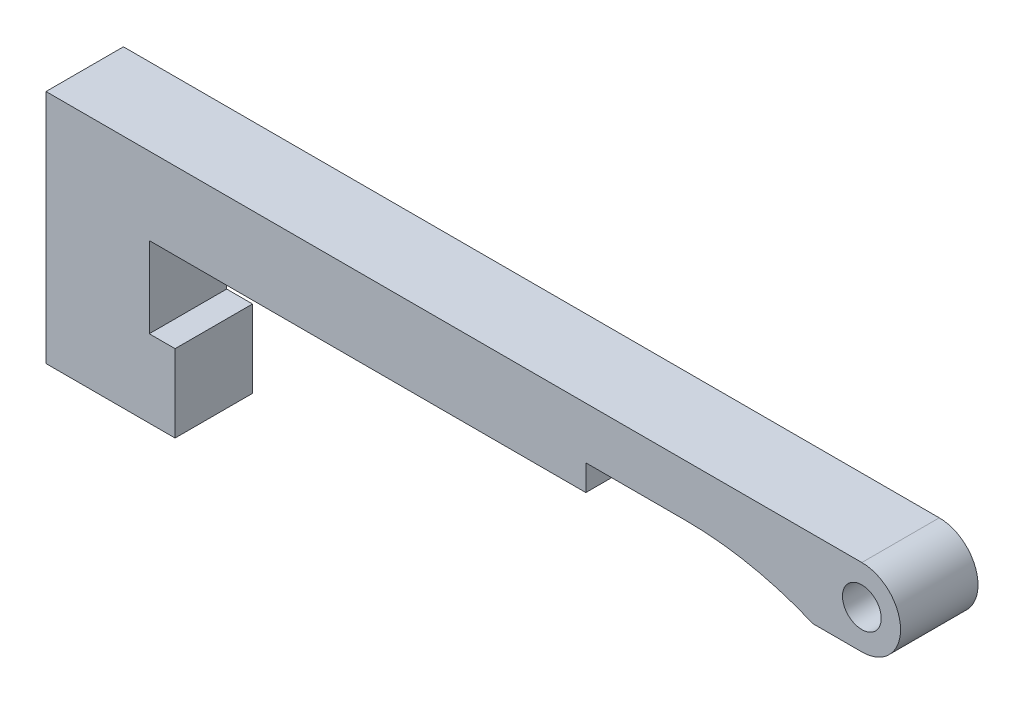
SolidWorks part; units mm, degrees
ref_plane "Front Plane" through (0, 0, 0) normal (0, 0, 1) x (1, 0, 0)
ref_plane "Top Plane" through (0, 0, 0) normal (0, 1, 0) x (1, 0, 0)
ref_plane "Right Plane" through (0, 0, 0) normal (1, 0, 0) x (0, 0, -1)
sketch "Sketch1" plane through (0, 0, 0) normal (0, 0, 1) x (1, 0, 0)
  line L0 (50, 0) -> (0, 0)
  line L1 (0, 0) -> (0, 91.2778)
  line L2 (0, 91.2778) -> (316.0534, 91.2778)
  line L4 (316.0534, 61.2778) -> (297.1173, 61.2778)
  line L5 (209.132, 61.2778) -> (40, 61.2778)
  line L6 (40, 61.2778) -> (40, 30)
  line L7 (40, 30) -> (50, 30)
  line L8 (50, 30) -> (50, 0)
  line L9 (209.132, 61.2778) -> (209.132, 71.2778)
  line L10 (209.132, 71.2778) -> (247.7691, 71.2778)
  arc A1 (297.1173, 61.2778) -> (247.7691, 71.2778) centre (247.7691, -55.4845) ccw
  circle A3 centre (316.0534, 76.2778) radius 7.5
  arc A4 (316.0534, 61.2778) -> (316.0534, 91.2778) centre (316.0534, 76.2778) ccw
  point P3 (0, 0)
  point P10 (259.8909, 73.9216)
  point P11 (196.9574, 82.1312)
  point P18 (297.1173, 121.9644)
  point P19 (225.9756, 75.3025)
  dimension "D5" = 15
  dimension "D6" = 30
  dimension "D1" = 40
  dimension "D2" = 10
  dimension "D3" = 30
  dimension "D4" = 30
  dimension "D7" = 10
extrude "Boss-Extrude1" add sketch "Sketch1" along normal blind 30
